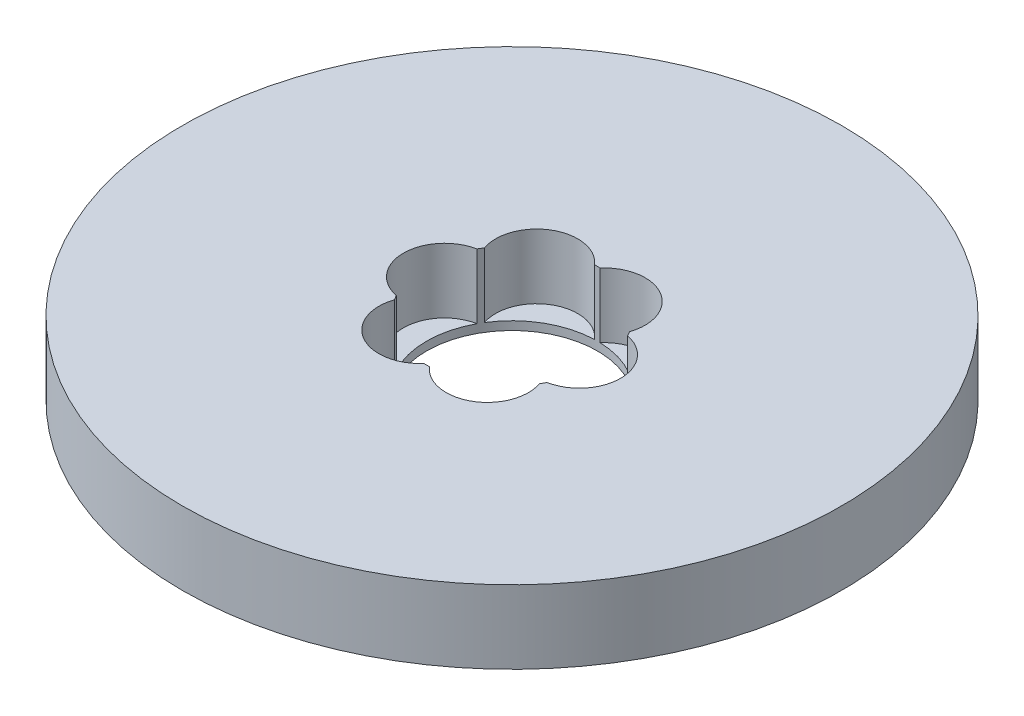
SolidWorks part; units mm, degrees
ref_plane "Front Plane" through (0, 0, 0) normal (0, 0, 1) x (1, 0, 0)
ref_plane "Top Plane" through (0, 0, 0) normal (0, 1, 0) x (1, 0, 0)
ref_plane "Right Plane" through (0, 0, 0) normal (1, 0, 0) x (0, 0, -1)
sketch "Sketch1" plane through (0, 0, 0) normal (0, 1, 0) x (1, 0, 0)
  circle A0 centre (0, 0) radius 67.5
  dimension "FLANGE_OD" = 135
extrude "Boss-Extrude1" add sketch "Sketch1" along normal blind 15
sketch "Sketch2" plane through (0, 0, 0) normal (0, 1, 0) x (1, 0, 0)
  circle A0 centre (0, 0) radius 17.5
  dimension "BORE_D" = 35
extrude "Cut-Extrude1" cut sketch "Sketch2" along normal through all
sketch "Sketch3" plane through (0, 15, 0) normal (0, 1, 0) x (1, 0, 0)
  circle A0 centre (0, 0) radius 13.8076 construction
  circle A1 centre (-13.8076, 0) radius 8.4209
  dimension "BOLT_D" = 16.8417
  dimension "BOLT_PCD" = 27.6151
extrude "Cut-Extrude2" cut sketch "Sketch3" against normal blind 13.2551
pattern_circular "CirPattern1" count 6 over 360 about axis through (0, 0, 0) along (0, 1, 0) of "Cut-Extrude2"
